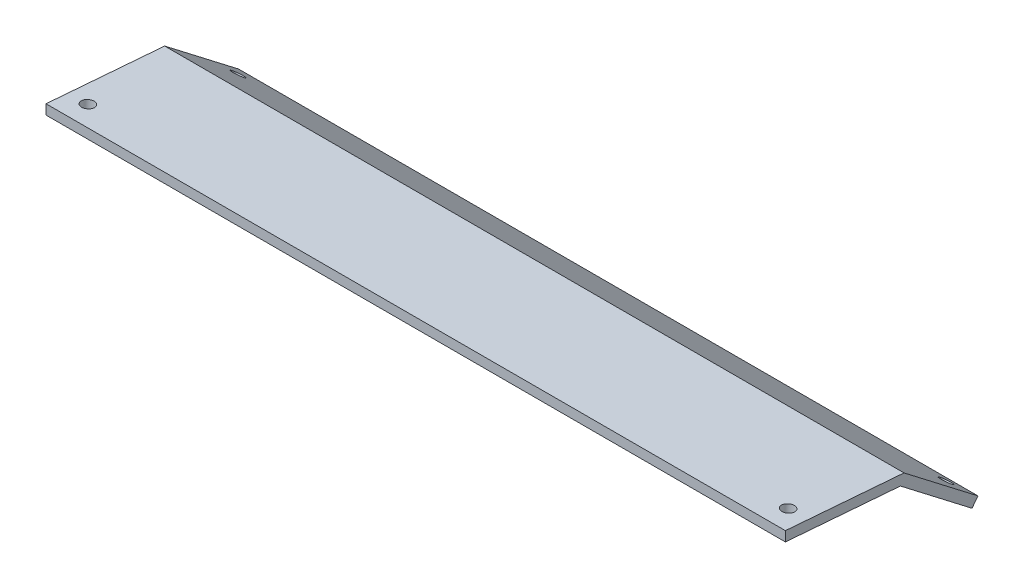
SolidWorks part; units mm, degrees
ref_plane "Front Plane" through (0, 0, 0) normal (0, 0, 1) x (1, 0, 0)
ref_plane "Top Plane" through (0, 0, 0) normal (0, 1, 0) x (1, 0, 0)
ref_plane "Right Plane" through (0, 0, 0) normal (1, 0, 0) x (0, 0, -1)
sketch "Sketch1" plane through (0, 0, 0) normal (1, 0, 0) x (0, 0, -1)
  line L7 (37.2768, -2.9328) -> (60.5049, -20.8002) construction
  line L8 (0, 0) -> (0, 3.1848)
  line L9 (0, 3.1848) -> (38.4655, 0.1584)
  line L10 (38.4655, 0.1584) -> (62.4407, -18.2836)
  line L11 (62.4407, -18.2836) -> (60.5049, -20.8002)
  line L12 (60.5049, -20.8002) -> (37.2768, -2.9328)
  line L13 (37.2768, -2.9328) -> (0, 0)
  arc A0 (59.9828, -23.0516) -> (60.9843, -21.6039) centre (59.7306, -21.8069) ccw construction
  arc A1 (59.9828, -23.0516) -> (60.5049, -20.8002) centre (59.7306, -21.8069) ccw construction
  dimension "D1" = 3.175
  dimension "D2" = 3.175
extrude "Boss-Extrude1" add sketch "Sketch1" along normal mid plane 239.7125
sketch "Sketch2" plane through (0, 3.1652, -0.249) normal (0, 0.9969, -0.0784) x (1, 0, 0)
  circle A0 centre (113.5062, 7.0049) radius 2.032
  circle A1 centre (-113.5063, 7.0049) radius 2.032
  dimension "D1" = 4.064
extrude "Cut-Extrude1" cut sketch "Sketch2" against normal through all
sketch "Sketch3" plane through (0, 18.6888, -14.3757) normal (0, 0.7926, -0.6097) x (1, 0, 0)
  circle A0 centre (-113.5062, 52.385) radius 2.032
  circle A1 centre (113.5062, 55.56) radius 2.032
  dimension "D1" = 4.064
extrude "Cut-Extrude2" cut sketch "Sketch3" against normal blind 12.7
